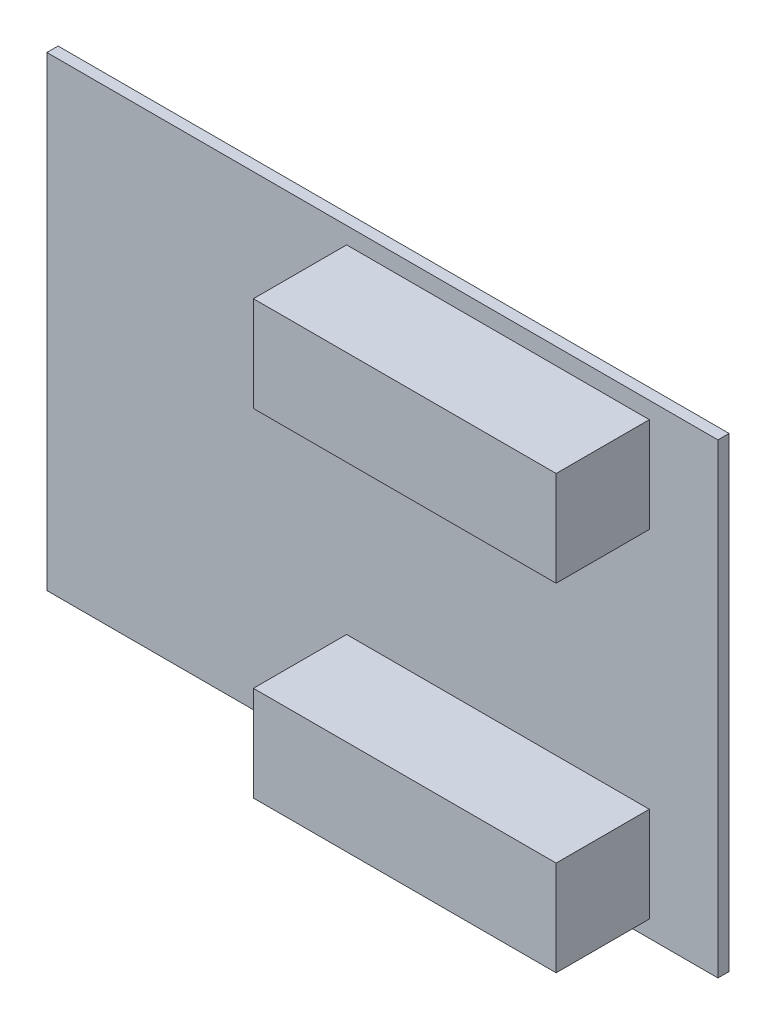
SolidWorks part; units mm, degrees
ref_plane "前视基准面" through (0, 0, 0) normal (0, 0, 1) x (1, 0, 0)
ref_plane "上视基准面" through (0, 0, 0) normal (0, 1, 0) x (1, 0, 0)
ref_plane "右视基准面" through (0, 0, 0) normal (1, 0, 0) x (0, 0, -1)
sketch "草图1" plane through (0, 0, 0) normal (0, 0, 1) x (1, 0, 0)
  line L1 (-90, 62.5) -> (90, 62.5)
  line L2 (-90, 62.5) -> (-90, -62.5)
  line L3 (-90, -62.5) -> (90, -62.5)
  line L4 (90, 62.5) -> (90, -62.5)
  line L5 (-90, 62.5) -> (90, -62.5) construction
  line L6 (-90, -62.5) -> (90, 62.5) construction
  point P0 (0, 0)
  dimension "D1" = 125
  dimension "D2" = 180
extrude "凸台-拉伸1" add sketch "草图1" along normal blind 3
sketch "草图7" plane through (0, 0, 0) normal (0, 0, -1) x (-1, 0, 0)
  line L0 (-90, 62.5) -> (90, 62.5) construction
  line L1 (-69.1, 55.5) -> (7.1, 55.5)
  line L2 (-69.1, 55.5) -> (-69.1, 35)
  line L3 (-69.1, 35) -> (7.1, 35)
  line L4 (7.1, 55.5) -> (7.1, 35)
  line L6 (-90, -62.5) -> (-90, 62.5) construction
  dimension "D1" = 20.5
  dimension "D2" = 76.2
  dimension "D3" = 7
  dimension "D4" = 20.9
extrude "电池位切除-拉伸3" cut sketch "草图7" against normal up to next
sketch "草图8" plane through (0, 0, 3) normal (0, 0, 1) x (1, 0, 0)
  line L12 (69.1, 55.5) -> (69.1, 35) construction
  line L13 (-9.6, 58) -> (71.6, 58)
  line L14 (-9.6, 58) -> (-9.6, 32.5)
  line L15 (-9.6, 32.5) -> (71.6, 32.5)
  line L16 (71.6, 58) -> (71.6, 32.5)
  line L17 (-7.1, 35) -> (-7.1, 55.5) construction
  line L18 (-7.1, 55.5) -> (69.1, 55.5) construction
  line L19 (69.1, 35) -> (-7.1, 35) construction
  line L20 (-7.1, 55.5) -> (69.1, 55.5)
  line L21 (69.1, 35) -> (-7.1, 35)
  line L22 (69.1, 55.5) -> (69.1, 35)
  line L23 (-7.1, 35) -> (-7.1, 55.5) construction
  line L24 (-7.1, 35) -> (-7.1, 55.5)
  dimension "D1" = 2.5
  dimension "D2" = 2.5
  dimension "D3" = 2.5
  dimension "D4" = 2.5
extrude "凸台-拉伸2" add sketch "草图8" along normal blind 25
sketch "草图9" plane through (0, 0, 28) normal (0, 0, 1) x (1, 0, 0)
  line L0 (71.6, 58) -> (-9.6, 58) construction
  line L5 (71.6, 58) -> (-9.6, 58)
  line L6 (-9.6, 32.5) -> (71.6, 32.5) construction
  line L7 (-9.6, 32.5) -> (71.6, 32.5)
  line L8 (71.6, 32.5) -> (71.6, 58) construction
  line L9 (71.6, 32.5) -> (71.6, 58)
  line L10 (-9.6, 58) -> (-9.6, 32.5) construction
  line L11 (-9.6, 58) -> (-9.6, 32.5)
extrude "凸台-拉伸3" add sketch "草图9" against normal blind 2.5
sketch "草图4" plane through (0, 0, 0) normal (0, 0, -1) x (-1, 0, 0)
  line L0 (7.1, 35) -> (7.1, 55.5) construction
  line L5 (7.1, 45.25) -> (84.6307, 45.25) construction
  line L10 (83.2374, -53.4277) -> (79.3374, -53.4277) construction
  line L11 (83.2374, -49.6277) -> (83.2374, -53.4277) construction
  line L12 (79.3374, -49.6277) -> (83.2374, -49.6277) construction
  line L29 (7.1, 41.25) -> (11.1, 41.25)
  line L30 (11.1, 41.25) -> (11.1, 49.25)
  line L31 (11.1, 49.25) -> (7.1, 49.25)
  line L32 (7.1, 49.25) -> (7.1, 41.25)
  dimension "D1" = 8
  dimension "D2" = 4
extrude "切除-拉伸2" cut sketch "草图4" along normal blind 1.6 from surface starting at face at (0, 0, 3)
mirror "镜向1" about plane through (0, 0, 0) normal (0, 1, 0) of "切除-拉伸2", "凸台-拉伸3", "凸台-拉伸2", "电池位切除-拉伸3"
